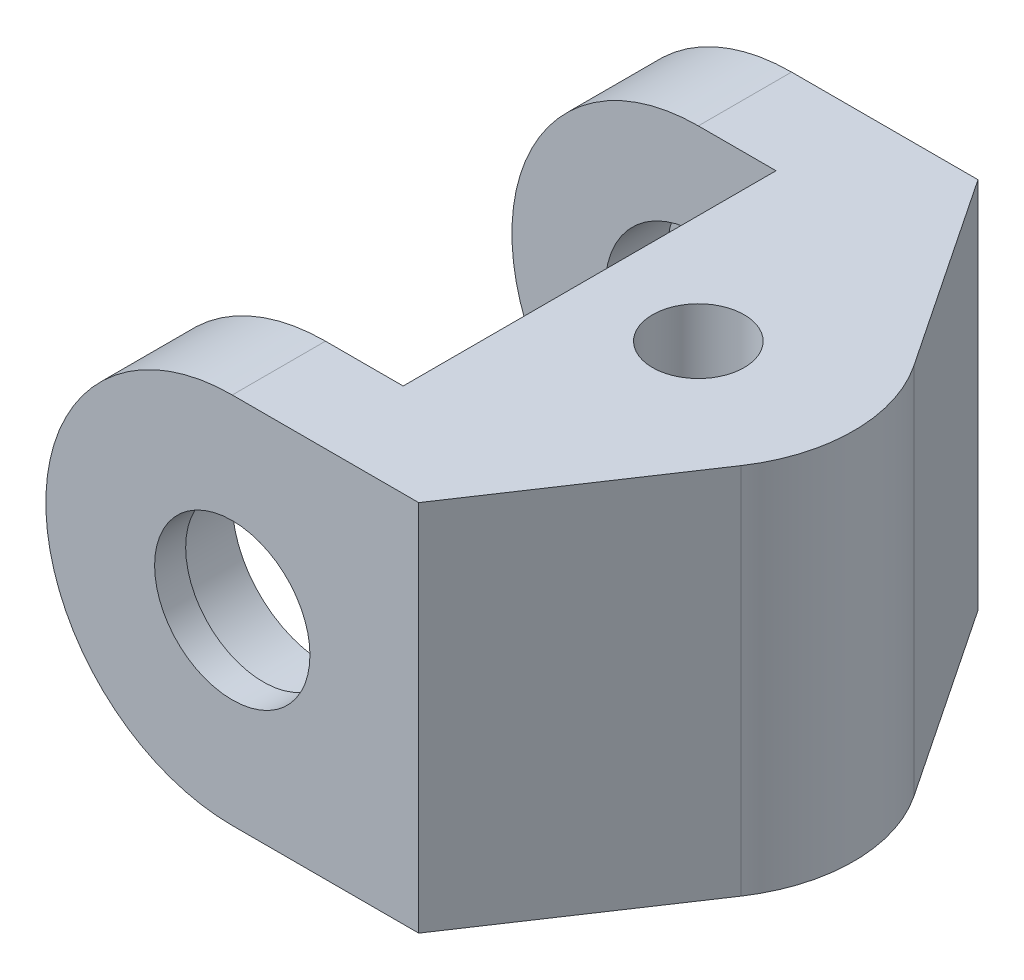
SolidWorks part; units mm, degrees
ref_plane "Front Plane" through (0, 0, 0) normal (0, 0, 1) x (1, 0, 0)
ref_plane "Top Plane" through (0, 0, 0) normal (0, 1, 0) x (1, 0, 0)
ref_plane "Right Plane" through (0, 0, 0) normal (1, 0, 0) x (0, 0, -1)
sketch "Sketch1" plane through (0, 0, 0) normal (0, 0, 1) x (1, 0, 0)
  circle A1 centre (-6, 0) radius 6
  circle A2 centre (-6, 0) radius 2.5
  dimension "D2" = 5
  dimension "D3" = 12
  dimension "D1" = 6
extrude "Boss-Extrude1" add sketch "Sketch1" along normal mid plane 18
sketch "Sketch2" plane through (0, 0, 0) normal (0, 1, 0) x (1, 0, 0)
  circle A0 centre (0, 0) radius 1.475
  circle A1 centre (0, 0) radius 5
  dimension "D1" = 10
  dimension "D2" = 2.95
extrude "Boss-Extrude2" add sketch "Sketch2" along normal mid plane 12
sketch "Sketch4" plane through (0, 0, 0) normal (0, 1, 0) x (1, 0, 0)
  line L0 (-6, 9) -> (-6, -9)
  line L1 (0, 9) -> (-12, 9) construction
  line L2 (-12, -9) -> (0, -9) construction
  line L3 (-6, -9) -> (0, -9)
  line L4 (0, -9) -> (4.1574, -2.7778)
  line L5 (4.1574, 2.7778) -> (0, 9)
  line L6 (0, 9) -> (-6, 9)
  line L7 (0, 5) -> (0, 9) construction
  circle A0 centre (0, 0) radius 5 construction
  arc A1 (4.1574, -2.7778) -> (4.1574, 2.7778) centre (0, 0) ccw
extrude "Boss-Extrude3" add sketch "Sketch4" along normal mid plane 12
sketch "Sketch3" plane through (0, 0, 0) normal (0, 1, 0) x (1, 0, 0)
  line L0 (-6, 12.2341) -> (-6, -14.1605) construction
  line L1 (-3.5, 8) -> (-3.5, 9)
  line L4 (-3.5, 8) -> (-3, 8)
  line L5 (-3, 8) -> (-3, 6)
  line L6 (-3, 6) -> (-1.5, 6)
  line L8 (-1.5, -6) -> (-3, -6)
  line L9 (-3, -6) -> (-3, -8)
  line L10 (-3, -8) -> (-3.5, -8)
  line L11 (-6, -9) -> (-6, 9)
  line L12 (-6, 9) -> (-8.5, 9) construction
  line L13 (0, 0) -> (-16.9033, 0) construction
  line L15 (0, 9) -> (-6, 9) construction
  line L16 (-3.5, 9) -> (-6, 9)
  line L17 (-3.5, -8) -> (-3.5, -9)
  line L18 (-3.5, -9) -> (-6, -9)
  line L19 (-1.5, 6) -> (-1.5, -6)
  line L20 (-6, 9) -> (-6, -9) construction
  dimension "D1" = 6
  dimension "D2" = 1
  dimension "D3" = 2
  dimension "D6" = 0.5
  dimension "D7" = 9
revolve "Cut-Revolve1" cut sketch "Sketch3" angle 360 about L0
sketch "Sketch5" plane through (0, 0, 0) normal (0, 1, 0) x (1, 0, 0)
  line L0 (-3.5, 6) -> (-3.5, -6)
  line L1 (-3.5, -6) -> (-12, -6)
  line L2 (-12, -6) -> (-12, 6)
  line L3 (-12, 6) -> (-3.5, 6)
  line L4 (-12, 9) -> (-12, -9) construction
  line L5 (-9, 6) -> (-3, 6) construction
  line L6 (-6, 9) -> (-6, -9) construction
  line L7 (0, 0) -> (-13.9863, 0) construction
  circle A0 centre (0, 0) radius 1.475
  circle A2 centre (0, 0) radius 1.475 construction
  dimension "D1" = 2.5
extrude "Cut-Extrude2" cut sketch "Sketch5" against normal through all both and the other way through all
combine bodies "Combine1" [suppressed] operation type add bodies to combine 111 112 111 111
ref_axis "Axis1" through (0, -8.4779, 0) along (0, 1, 0)
ref_axis "Axis2" through (-6, 0, 11.4241) along (0, 0, -1)
